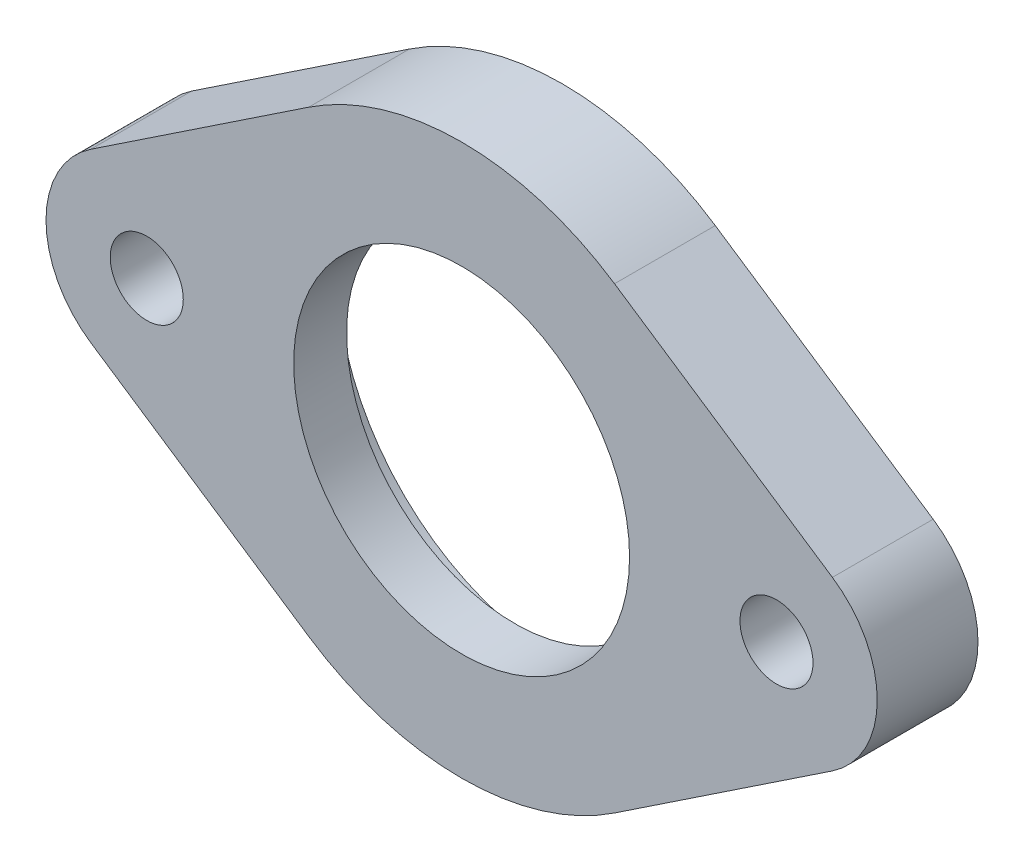
SolidWorks part; units mm, degrees
material "ABS"
ref_plane "Front Plane" through (0, 0, 0) normal (0, 0, 1) x (1, 0, 0)
ref_plane "Top Plane" through (0, 0, 0) normal (0, 1, 0) x (1, 0, 0)
ref_plane "Right Plane" through (0, 0, 0) normal (1, 0, 0) x (0, 0, -1)
sketch "Sketch1" plane through (0, 0, 0) normal (0, 0, 1) x (1, 0, 0)
  line L0 (-12.5, 0) -> (12.5, 0)
  line L1 (-6.0703, -9.0984) -> (-14.72, -3.3274)
  line L2 (-6.0703, 9.0984) -> (-14.72, 3.3274)
  line L3 (6.0703, 9.0984) -> (14.72, 3.3274)
  line L4 (6.0703, -9.0984) -> (14.72, -3.3274)
  circle A0 centre (0, 0) radius 6.6675
  circle A1 centre (0, 0) radius 8.9375
  circle A2 centre (0, 0) radius 10.9375
  circle A3 centre (-12.5, 0) radius 4
  circle A4 centre (12.5, 0) radius 4
  point P7 (0, 0)
  dimension "D1" = 13.335
  dimension "D2" = 17.875
  dimension "D4" = 8
  dimension "D3" = 2
  dimension "D5" = 25
extrude "Boss-Extrude1" add sketch "Sketch1" along normal blind 4 contours A3 L0 A2 L2 | A3 L1 A2 L0 | A3 | A4 L3 A2 L0 | A4 | A4 L0 A2 L4 | A2 region at (13.2988, 0, 0) region at (10.617, 5.2562, 0) region at (10.617, -5.2562, 0) region at (-10.617, 5.2562, 0) region at (-13.2988, 0, 0) region at (-10.617, -5.2562, 0)
extrude "Cut-Extrude1" cut sketch "Sketch1<4>" against normal through all both and the other way through all contours L0 A0 | L0 A0 region at (0, -2.8298, 0) region at (0, 2.8298, 0)
sketch "Sketch1<4>" plane through (0, 0, 0) normal (0, 0, 1) x (1, 0, 0) same geometry as "Sketch1"
extrude "Cut-Extrude2" cut sketch "Sketch1<6>" along normal blind 1.9 and the other way through all contours A1
sketch "Sketch1<6>" plane through (0, 0, 0) normal (0, 0, 1) x (1, 0, 0) same geometry as "Sketch1"
sketch "Sketch2" plane through (0, 0, 4) normal (0, 0, 1) x (1, 0, 0)
  point P0 (-12.5, 0)
  point P3 (12.5, 0)
hole_wizard "M2.5 Clearance Hole1" positions "Sketch2" profile "Sketch3" hole size "M2.5" standard "ANSI Metric" end condition through all
sketch "Sketch3" plane through (-12.5, 0, 4) normal (1, 0, 0) x (0, -1, 0)
  line L0 (0, 0) -> (0, 4)
  line L1 (0, 4) -> (1.45, 4)
  line L2 (1.45, 4) -> (1.45, 0)
  line L5 (1.45, 0) -> (0, 0)
  line L11 (0, -6.35) -> (0, 107.95) construction
  dimension "Thru Hole Dia." = 2.9
  dimension "Thru Hole Depth" = 4
equation "\"D2@Sketch1\"=15.875mm+2"
